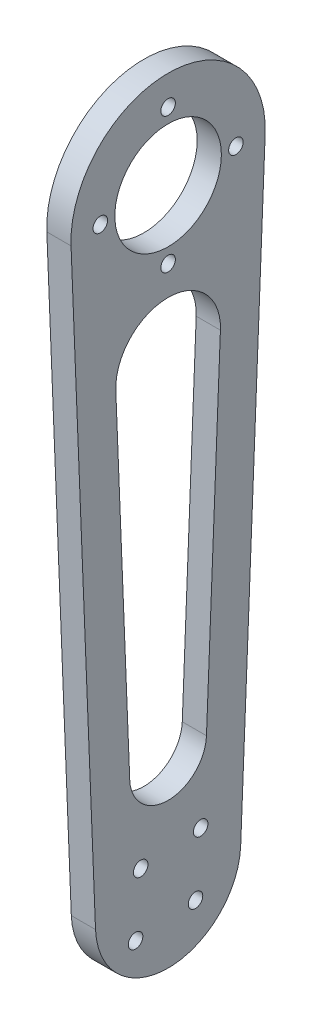
SolidWorks part; units mm, degrees
material "6061-T6 (SS)"
ref_plane "Front Plane" through (0, 0, 0) normal (1, 0, 0) x (0, 1, 0)
ref_plane "Top Plane" through (0, 0, 0) normal (0, 0, 1) x (0, 1, 0)
ref_plane "Right Plane" through (0, 0, 0) normal (0, 1, 0) x (-1, 0, 0)
sketch "Sketch1" plane through (0, 0, 0) normal (1, 0, 0) x (0, 1, 0)
  line L0 (-125, 0) -> (-115.5, 0)
  line L1 (-119.3431, 5.6569) -> (-130.6569, -5.6569) construction
  line L2 (-131.7175, 6.7175) -> (-118.2825, -6.7175) construction
  line L3 (-125.6072, 14.9877) -> (-0.812, 20.0436)
  line L4 (-125.6072, -14.9877) -> (-0.812, -20.0436)
  line L5 (-125.2834, -6.9943) -> (-0.4882, -12.0501) construction
  line L6 (-102.3928, 7.9216) -> (-31.308, 10.8015)
  line L8 (-102.3928, -7.9216) -> (-31.308, -10.8015)
  circle A0 centre (0, 0) radius 14 construction
  circle A1 centre (0, 14) radius 1.5
  circle A2 centre (-14, 0) radius 1.5
  circle A3 centre (14, 0) radius 1.5
  circle A4 centre (0, -14) radius 1.5
  circle A5 centre (0, 0) radius 11
  circle A6 centre (0, 0) radius 20.06
  circle A7 centre (-125, 0) radius 8 construction
  circle A8 centre (-125, 0) radius 9.5 construction
  circle A9 centre (-131.7175, 6.7175) radius 1.5
  circle A10 centre (-118.2825, -6.7175) radius 1.5
  circle A11 centre (-119.3431, 5.6569) radius 1.5
  circle A12 centre (-130.6569, -5.6569) radius 1.5
  circle A13 centre (-125, 0) radius 15
  arc A14 (-102.3928, 7.9216) -> (-102.3928, -7.9216) centre (-102.0719, 0) ccw
  arc A15 (-31.308, -10.8015) -> (-31.308, 10.8015) centre (-30.8704, 0) ccw
  dimension "D1" = 28
  dimension "D2" = 3
  dimension "D3" = 22
  dimension "D4" = 40.12
  dimension "D5" = 16
  dimension "D6" = 19
  dimension "D10" = 3
  dimension "D11" = 30
  dimension "D7" = 90
  dimension "D8" = 45
  dimension "D9" = 125
  dimension "D12" = 8
  dimension "D13" = 8
extrude "Boss-Extrude1" add sketch "Sketch1" along normal blind 5 contours A15 A6 L3 A13 A14 L6 | A15 L8 A14 A13 L4 A6 | A13 A12 A11 A10 A9 | A6 A1 A2 A3 A4 A5 region at (0, -62.86, 13.2515) region at (0, -114.9042, 10.5131) region at (0, 13.5015, 14.0596) region at (0, -62.86, -13.2515)
